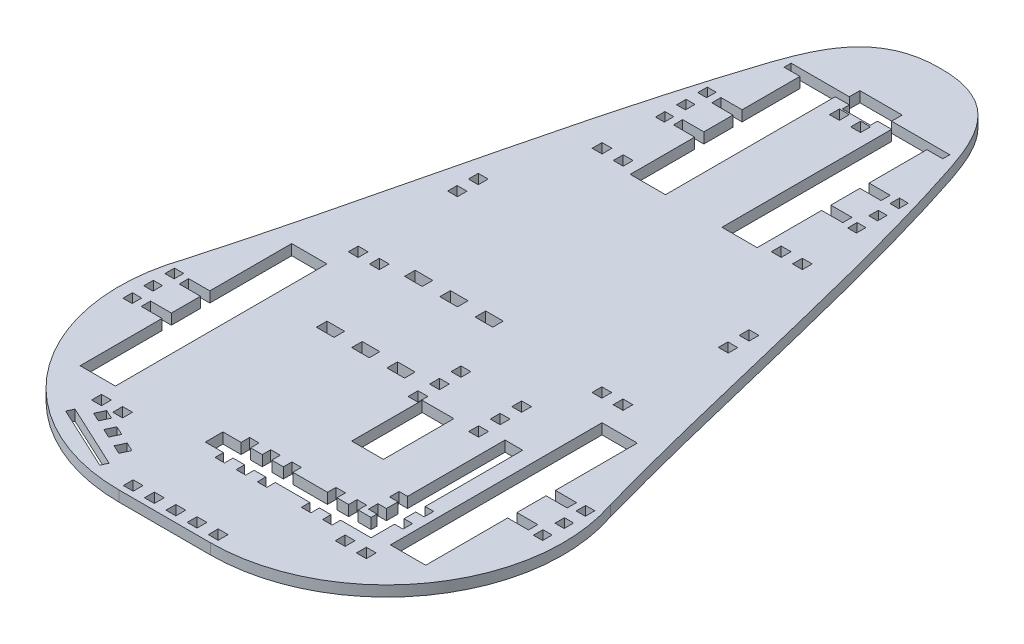
SolidWorks part; units mm, degrees
ref_plane "Front Plane" through (0, 0, 0) normal (0, 0, 1) x (1, 0, 0)
ref_plane "Top Plane" through (0, 0, 0) normal (0, 1, 0) x (1, 0, 0)
ref_plane "Right Plane" through (0, 0, 0) normal (1, 0, 0) x (0, 0, -1)
sketch "Sketch1" plane through (0, 0, 0) normal (0, 1, 0) x (1, 0, 0)
  line L0 (54.872, 210.7624) -> (54.872, -9.2376) construction
  line L1 (41.9035, -9.2376) -> (67.8405, -9.2376)
  line L6 (5.872, 75.7624) -> (15.872, 75.7624)
  line L7 (54.872, -9.2376) -> (64.872, -9.2376)
  line L8 (54.872, -9.2376) -> (44.872, -9.2376)
  line L9 (5.872, 75.7624) -> (5.872, 15.7624)
  line L10 (5.872, 15.7624) -> (15.872, 15.7624)
  line L11 (15.872, 75.7624) -> (15.872, 15.7624)
  line L12 (5.872, 75.7624) -> (15.872, 15.7624) construction
  line L13 (5.872, 15.7624) -> (15.872, 75.7624) construction
  line L18 (-0.128, 52.5374) -> (5.872, 52.5374)
  line L19 (-0.128, 52.5374) -> (-0.128, 49.8874)
  line L35 (103.872, 15.7624) -> (93.872, 15.7624)
  line L36 (93.872, 75.7624) -> (93.872, 15.7624)
  line L37 (103.872, 75.7624) -> (93.872, 75.7624)
  line L38 (103.872, 75.7624) -> (103.872, 15.7624)
  line L40 (36.872, 190.7624) -> (46.872, 190.7624)
  line L41 (36.872, 190.7624) -> (36.872, 140.7624)
  line L42 (36.872, 140.7624) -> (46.872, 140.7624)
  line L43 (46.872, 190.7624) -> (46.872, 140.7624)
  line L44 (36.872, 190.7624) -> (46.872, 140.7624) construction
  line L45 (36.872, 140.7624) -> (46.872, 190.7624) construction
  line L46 (10.872, 45.7624) -> (-10.2667, 45.7624) construction
  line L63 (72.872, 140.7624) -> (62.872, 140.7624)
  line L64 (62.872, 190.7624) -> (62.872, 140.7624)
  line L65 (72.872, 190.7624) -> (62.872, 190.7624)
  line L66 (72.872, 190.7624) -> (72.872, 140.7624)
  line L78 (114.472, 47.1124) -> (111.872, 44.4124) construction
  line L79 (114.472, 44.4124) -> (111.872, 47.1124) construction
  line L80 (114.472, 50.4124) -> (111.872, 53.1124) construction
  line L81 (114.472, 53.1124) -> (111.872, 50.4124) construction
  line L82 (109.7728, 38.9874) -> (103.7728, 41.6374) construction
  line L83 (109.7728, 41.6374) -> (103.7728, 38.9874) construction
  line L84 (109.872, 49.8874) -> (103.872, 52.5374) construction
  line L85 (109.872, 52.5374) -> (103.872, 49.8874) construction
  line L86 (111.7728, 41.1124) -> (111.7728, 38.4124)
  line L87 (114.3728, 38.4124) -> (111.7728, 38.4124)
  line L88 (114.3728, 41.1124) -> (114.3728, 38.4124)
  line L89 (111.872, 44.4124) -> (111.872, 47.1124)
  line L90 (114.472, 47.1124) -> (111.872, 47.1124)
  line L91 (114.472, 44.4124) -> (114.472, 47.1124)
  line L92 (41.872, 165.7624) -> (24.9145, 165.7624) construction
  line L93 (30.872, 172.4874) -> (36.872, 172.4874)
  line L94 (30.872, 172.4874) -> (30.872, 169.8874)
  line L95 (30.872, 169.8874) -> (36.872, 169.8874)
  line L96 (36.872, 172.4874) -> (36.872, 169.8874)
  line L97 (30.872, 172.4874) -> (36.872, 169.8874) construction
  line L98 (30.872, 169.8874) -> (36.872, 172.4874) construction
  line L103 (26.372, 161.1124) -> (28.872, 161.1124)
  line L104 (26.372, 173.1124) -> (28.872, 173.1124)
  line L105 (30.872, 161.6374) -> (36.872, 161.6374)
  line L106 (30.872, 161.6374) -> (30.872, 159.0374)
  line L107 (30.872, 159.0374) -> (36.872, 159.0374)
  line L108 (36.872, 161.6374) -> (36.872, 159.0374)
  line L109 (30.872, 161.6374) -> (36.872, 159.0374) construction
  line L110 (30.872, 159.0374) -> (36.872, 161.6374) construction
  line L111 (26.372, 173.1124) -> (26.372, 170.4124)
  line L112 (26.372, 170.4124) -> (28.872, 170.4124)
  line L113 (28.872, 173.1124) -> (28.872, 170.4124)
  line L114 (26.372, 173.1124) -> (28.872, 170.4124) construction
  line L115 (26.372, 170.4124) -> (28.872, 173.1124) construction
  line L116 (26.372, 164.4124) -> (28.872, 164.4124)
  line L117 (26.372, 164.4124) -> (26.372, 167.1124)
  line L118 (26.372, 167.1124) -> (28.872, 167.1124)
  line L119 (28.872, 164.4124) -> (28.872, 167.1124)
  line L120 (26.372, 164.4124) -> (28.872, 167.1124) construction
  line L121 (26.372, 167.1124) -> (28.872, 164.4124) construction
  line L122 (26.372, 161.1124) -> (26.372, 158.4124)
  line L123 (26.372, 158.4124) -> (28.872, 158.4124)
  line L124 (28.872, 161.1124) -> (28.872, 158.4124)
  line L125 (83.372, 167.1124) -> (80.872, 164.4124) construction
  line L126 (83.372, 164.4124) -> (80.872, 167.1124) construction
  line L127 (83.372, 170.4124) -> (80.872, 173.1124) construction
  line L128 (83.372, 173.1124) -> (80.872, 170.4124) construction
  line L129 (78.872, 159.0374) -> (72.872, 161.6374) construction
  line L130 (78.872, 161.6374) -> (72.872, 159.0374) construction
  line L131 (78.872, 169.8874) -> (72.872, 172.4874) construction
  line L132 (78.872, 172.4874) -> (72.872, 169.8874) construction
  line L133 (80.872, 161.1124) -> (80.872, 158.4124)
  line L134 (83.372, 158.4124) -> (80.872, 158.4124)
  line L135 (83.372, 161.1124) -> (83.372, 158.4124)
  line L136 (80.872, 164.4124) -> (80.872, 167.1124)
  line L137 (83.372, 167.1124) -> (80.872, 167.1124)
  line L138 (83.372, 164.4124) -> (83.372, 167.1124)
  line L139 (83.372, 164.4124) -> (80.872, 164.4124)
  line L140 (80.872, 173.1124) -> (80.872, 170.4124)
  line L141 (83.372, 170.4124) -> (80.872, 170.4124)
  line L142 (83.372, 173.1124) -> (83.372, 170.4124)
  line L143 (72.872, 161.6374) -> (72.872, 159.0374)
  line L144 (78.872, 159.0374) -> (72.872, 159.0374)
  line L145 (78.872, 161.6374) -> (78.872, 159.0374)
  line L146 (78.872, 161.6374) -> (72.872, 161.6374)
  line L147 (83.372, 173.1124) -> (80.872, 173.1124)
  line L148 (83.372, 161.1124) -> (80.872, 161.1124)
  line L149 (72.872, 172.4874) -> (72.872, 169.8874)
  line L150 (78.872, 169.8874) -> (72.872, 169.8874)
  line L151 (78.872, 172.4874) -> (78.872, 169.8874)
  line L152 (78.872, 172.4874) -> (72.872, 172.4874)
  line L153 (-0.128, 49.8874) -> (5.872, 49.8874)
  line L154 (5.872, 52.5374) -> (5.872, 49.8874)
  line L155 (-0.128, 52.5374) -> (5.872, 49.8874) construction
  line L156 (-0.128, 49.8874) -> (5.872, 52.5374) construction
  line L157 (-4.6289, 41.1124) -> (-2.0289, 41.1124)
  line L158 (-4.728, 53.1124) -> (-2.128, 53.1124)
  line L159 (-0.0289, 41.6374) -> (5.9711, 41.6374)
  line L160 (-0.0289, 41.6374) -> (-0.0289, 38.9874)
  line L161 (-0.0289, 38.9874) -> (5.9711, 38.9874)
  line L162 (5.9711, 41.6374) -> (5.9711, 38.9874)
  line L163 (-0.0289, 41.6374) -> (5.9711, 38.9874) construction
  line L164 (-0.0289, 38.9874) -> (5.9711, 41.6374) construction
  line L165 (-4.728, 53.1124) -> (-4.728, 50.4124)
  line L166 (-4.728, 50.4124) -> (-2.128, 50.4124)
  line L167 (-2.128, 53.1124) -> (-2.128, 50.4124)
  line L168 (-4.728, 53.1124) -> (-2.128, 50.4124) construction
  line L169 (-4.728, 50.4124) -> (-2.128, 53.1124) construction
  line L170 (-4.728, 44.4124) -> (-2.128, 44.4124)
  line L171 (-4.728, 44.4124) -> (-4.728, 47.1124)
  line L172 (-4.728, 47.1124) -> (-2.128, 47.1124)
  line L173 (-2.128, 44.4124) -> (-2.128, 47.1124)
  line L174 (-4.728, 44.4124) -> (-2.128, 47.1124) construction
  line L175 (-4.728, 47.1124) -> (-2.128, 44.4124) construction
  line L176 (-4.6289, 41.1124) -> (-4.6289, 38.4124)
  line L177 (-4.6289, 38.4124) -> (-2.0289, 38.4124)
  line L178 (-2.0289, 41.1124) -> (-2.0289, 38.4124)
  line L179 (114.472, 44.4124) -> (111.872, 44.4124)
  line L180 (111.872, 53.1124) -> (111.872, 50.4124)
  line L181 (114.472, 50.4124) -> (111.872, 50.4124)
  line L182 (114.472, 53.1124) -> (114.472, 50.4124)
  line L183 (103.7728, 41.6374) -> (103.7728, 38.9874)
  line L184 (109.7728, 38.9874) -> (103.7728, 38.9874)
  line L185 (109.7728, 41.6374) -> (109.7728, 38.9874)
  line L186 (109.7728, 41.6374) -> (103.7728, 41.6374)
  line L187 (114.472, 53.1124) -> (111.872, 53.1124)
  line L188 (114.3728, 41.1124) -> (111.7728, 41.1124)
  line L189 (103.872, 52.5374) -> (103.872, 49.8874)
  line L190 (109.872, 49.8874) -> (103.872, 49.8874)
  line L191 (109.872, 52.5374) -> (109.872, 49.8874)
  line L192 (109.872, 52.5374) -> (103.872, 52.5374)
  line L193 (103.872, 45.7624) -> (5.872, 45.7624) construction
  line L200 (62.872, 55.7624) -> (71.872, 55.7624)
  line L201 (62.872, 55.7624) -> (62.872, 35.7624)
  line L202 (62.872, 35.7624) -> (71.872, 35.7624)
  line L203 (71.872, 55.7624) -> (71.872, 35.7624)
  line L204 (62.872, 55.7624) -> (71.872, 35.7624) construction
  line L205 (62.872, 35.7624) -> (71.872, 55.7624) construction
  line L211 (39.9211, 61.7172) -> (44.9211, 61.7172)
  line L213 (59.9211, 69.7172) -> (62.7211, 69.7172)
  line L214 (59.9211, 57.5172) -> (62.7211, 57.5172)
  line L215 (59.9211, 57.5172) -> (59.9211, 54.7172)
  line L216 (59.9211, 54.7172) -> (62.7211, 54.7172)
  line L217 (62.7211, 57.5172) -> (62.7211, 54.7172)
  line L218 (59.9211, 57.5172) -> (62.7211, 54.7172) construction
  line L219 (59.9211, 54.7172) -> (62.7211, 57.5172) construction
  line L220 (59.9211, 69.7172) -> (59.9211, 66.9172)
  line L221 (59.9211, 66.9172) -> (62.7211, 66.9172)
  line L222 (62.7211, 69.7172) -> (62.7211, 66.9172)
  line L223 (59.9211, 63.6172) -> (62.7211, 63.6172)
  line L224 (59.9211, 63.6172) -> (59.9211, 60.8172)
  line L225 (59.9211, 60.8172) -> (62.7211, 60.8172)
  line L226 (62.7211, 63.6172) -> (62.7211, 60.8172)
  line L227 (77.1211, 69.7172) -> (79.9211, 69.7172)
  line L228 (77.1211, 57.5172) -> (79.9211, 57.5172)
  line L229 (77.1211, 57.5172) -> (77.1211, 54.7172)
  line L230 (77.1211, 54.7172) -> (79.9211, 54.7172)
  line L231 (79.9211, 57.5172) -> (79.9211, 54.7172)
  line L232 (77.1211, 69.7172) -> (77.1211, 66.9172)
  line L233 (77.1211, 66.9172) -> (79.9211, 66.9172)
  line L234 (79.9211, 69.7172) -> (79.9211, 66.9172)
  line L235 (77.1211, 63.6172) -> (79.9211, 63.6172)
  line L236 (77.1211, 63.6172) -> (77.1211, 60.8172)
  line L237 (77.1211, 60.8172) -> (79.9211, 60.8172)
  line L238 (79.9211, 63.6172) -> (79.9211, 60.8172)
  line L244 (49.9211, 61.7172) -> (54.9211, 61.7172)
  line L245 (49.9211, 61.7172) -> (49.9211, 58.7172)
  line L246 (49.9211, 58.7172) -> (54.9211, 58.7172)
  line L247 (54.9211, 61.7172) -> (54.9211, 58.7172)
  line L248 (49.9211, 61.7172) -> (54.9211, 58.7172) construction
  line L249 (49.9211, 58.7172) -> (54.9211, 61.7172) construction
  line L250 (39.9211, 61.7172) -> (39.9211, 58.7172)
  line L251 (39.9211, 58.7172) -> (44.9211, 58.7172)
  line L252 (44.9211, 61.7172) -> (44.9211, 58.7172)
  line L253 (29.9211, 61.7172) -> (34.9211, 61.7172)
  line L254 (29.9211, 61.7172) -> (29.9211, 58.7172)
  line L255 (29.9211, 58.7172) -> (34.9211, 58.7172)
  line L256 (34.9211, 61.7172) -> (34.9211, 58.7172)
  line L257 (49.9211, 86.7172) -> (54.9211, 86.7172)
  line L258 (49.9211, 86.7172) -> (49.9211, 83.7172)
  line L259 (49.9211, 83.7172) -> (54.9211, 83.7172)
  line L260 (54.9211, 86.7172) -> (54.9211, 83.7172)
  line L261 (39.9211, 86.7172) -> (44.9211, 86.7172)
  line L262 (39.9211, 86.7172) -> (39.9211, 83.7172)
  line L263 (39.9211, 83.7172) -> (44.9211, 83.7172)
  line L264 (44.9211, 86.7172) -> (44.9211, 83.7172)
  line L265 (29.9211, 86.7172) -> (34.9211, 86.7172)
  line L266 (29.9211, 86.7172) -> (29.9211, 83.7172)
  line L267 (29.9211, 83.7172) -> (34.9211, 83.7172)
  line L268 (34.9211, 86.7172) -> (34.9211, 83.7172)
  line L279 (15.072, 113.4624) -> (17.872, 113.4624)
  line L284 (15.0729, 119.4624) -> (17.8729, 119.4624)
  line L285 (15.0729, 119.4624) -> (15.0729, 116.6624)
  line L286 (15.0729, 116.6624) -> (17.8729, 116.6624)
  line L287 (17.8729, 119.4624) -> (17.8729, 116.6624)
  line L288 (15.072, 113.4624) -> (15.072, 110.7624)
  line L289 (15.072, 110.7624) -> (17.872, 110.7624)
  line L290 (17.872, 113.4624) -> (17.872, 110.7624)
  line L291 (318.4893, 36.945) -> (321.2893, 36.945)
  line L292 (243.2893, 39.945) -> (321.2893, 39.945)
  line L293 (243.2893, 39.945) -> (243.2893, -41.655)
  line L294 (243.2893, -41.655) -> (321.2893, -41.655)
  line L295 (321.2893, 39.945) -> (321.2893, -41.655)
  line L296 (243.2893, 36.945) -> (246.0893, 36.945)
  line L297 (243.2893, 36.945) -> (243.2893, 34.145)
  line L298 (243.2893, 34.145) -> (246.0893, 34.145)
  line L299 (246.0893, 36.945) -> (246.0893, 34.145)
  line L300 (318.4893, 36.945) -> (318.4893, 34.145)
  line L301 (318.4893, 34.145) -> (321.2893, 34.145)
  line L302 (321.2893, 36.945) -> (321.2893, 34.145)
  line L303 (249.2893, 36.945) -> (252.0893, 36.945)
  line L304 (249.2893, 36.945) -> (249.2893, 34.145)
  line L305 (249.2893, 34.145) -> (252.0893, 34.145)
  line L306 (252.0893, 36.945) -> (252.0893, 34.145)
  line L307 (312.4893, 36.945) -> (315.2893, 36.945)
  line L308 (312.4893, 36.945) -> (312.4893, 34.145)
  line L309 (312.4893, 34.145) -> (315.2893, 34.145)
  line L310 (315.2893, 36.945) -> (315.2893, 34.145)
  line L311 (318.4893, -35.855) -> (321.2893, -35.855)
  line L312 (243.2893, -35.855) -> (246.0893, -35.855)
  line L313 (243.2893, -35.855) -> (243.2893, -38.655)
  line L314 (243.2893, -38.655) -> (246.0893, -38.655)
  line L315 (246.0893, -35.855) -> (246.0893, -38.655)
  line L316 (318.4893, -35.855) -> (318.4893, -38.655)
  line L317 (318.4893, -38.655) -> (321.2893, -38.655)
  line L318 (321.2893, -35.855) -> (321.2893, -38.655)
  line L319 (249.2893, -35.855) -> (252.0893, -35.855)
  line L320 (249.2893, -35.855) -> (249.2893, -38.655)
  line L321 (249.2893, -38.655) -> (252.0893, -38.655)
  line L322 (252.0893, -35.855) -> (252.0893, -38.655)
  line L323 (312.4893, -35.855) -> (315.2893, -35.855)
  line L324 (312.4893, -35.855) -> (312.4893, -38.655)
  line L325 (312.4893, -38.655) -> (315.2893, -38.655)
  line L326 (315.2893, -35.855) -> (315.2893, -38.655)
  line L332 (15.9201, 84.5624) -> (18.7201, 84.5624)
  line L333 (15.9201, 84.5624) -> (15.9201, 81.7624)
  line L334 (15.9201, 81.7624) -> (18.7201, 81.7624)
  line L335 (18.7201, 84.5624) -> (18.7201, 81.7624)
  line L339 (21.9201, 84.5624) -> (24.7201, 84.5624)
  line L340 (21.9201, 84.5624) -> (21.9201, 81.7624)
  line L341 (21.9201, 81.7624) -> (24.7201, 81.7624)
  line L342 (24.7201, 84.5624) -> (24.7201, 81.7624)
  line L348 (15.9201, 11.7624) -> (18.7201, 11.7624)
  line L349 (15.9201, 11.7624) -> (15.9201, 8.9624)
  line L350 (15.9201, 8.9624) -> (18.7201, 8.9624)
  line L351 (18.7201, 11.7624) -> (18.7201, 8.9624)
  line L355 (21.9201, 11.7624) -> (24.7201, 11.7624)
  line L356 (21.9201, 11.7624) -> (21.9201, 8.9624)
  line L357 (21.9201, 8.9624) -> (24.7201, 8.9624)
  line L358 (24.7201, 11.7624) -> (24.7201, 8.9624)
  line L363 (25.072, 144.5629) -> (27.872, 144.5629)
  line L368 (25.072, 144.5629) -> (25.072, 141.7629)
  line L369 (25.072, 141.7629) -> (27.872, 141.7629)
  line L370 (27.872, 144.5629) -> (27.872, 141.7629)
  line L371 (31.072, 144.5624) -> (33.872, 144.5624)
  line L372 (31.072, 144.5624) -> (31.072, 141.7624)
  line L373 (31.072, 141.7624) -> (33.872, 141.7624)
  line L374 (33.872, 144.5624) -> (33.872, 141.7624)
  line L375 (75.872, 144.5624) -> (75.872, 141.7624)
  line L376 (78.672, 141.7624) -> (75.872, 141.7624)
  line L377 (78.672, 144.5624) -> (78.672, 141.7624)
  line L378 (78.672, 144.5624) -> (75.872, 144.5624)
  line L379 (81.872, 144.5629) -> (81.872, 141.7629)
  line L380 (84.672, 141.7629) -> (81.872, 141.7629)
  line L381 (84.672, 144.5629) -> (84.672, 141.7629)
  line L382 (84.672, 144.5629) -> (81.872, 144.5629)
  line L383 (50.4739, 186.4794) -> (50.472, 183.6794)
  line L384 (32.372, 190.884) -> (77.372, 190.884)
  line L385 (32.372, 190.884) -> (32.372, 188.884)
  line L386 (32.372, 188.884) -> (77.372, 188.884)
  line L387 (77.372, 190.884) -> (77.372, 188.884)
  line L388 (48.872, 193.884) -> (60.872, 193.884)
  line L389 (48.872, 193.884) -> (48.872, 190.884)
  line L390 (48.872, 190.884) -> (60.872, 190.884)
  line L391 (60.872, 193.884) -> (60.872, 190.884)
  line L392 (53.272, 183.6794) -> (50.472, 183.6794)
  line L393 (53.272, 186.4794) -> (53.272, 183.6794)
  line L394 (53.272, 186.4794) -> (50.4739, 186.4794)
  line L404 (85.372, 55.7624) -> (88.372, 55.7624)
  line L405 (85.372, 55.7624) -> (85.372, 15.7624)
  line L406 (85.372, 15.7624) -> (88.372, 15.7624)
  line L407 (88.372, 55.7624) -> (88.372, 15.7624)
  line L408 (44.372, 18.7624) -> (88.372, 18.7624)
  line L409 (44.372, 18.7624) -> (44.372, 15.7624)
  line L410 (44.372, 15.7624) -> (88.372, 15.7624)
  line L411 (88.372, 18.7624) -> (88.372, 15.7624)
  line L471 (41.9035, -9.2376) -> (64.872, -9.2376)
  line L480 (47.522, 22.1624) -> (47.522, 19.7624)
  line L481 (50.222, 19.7624) -> (47.522, 19.7624)
  line L482 (50.222, 22.1624) -> (50.222, 19.7624)
  line L483 (50.222, 22.1624) -> (47.522, 22.1624)
  line L484 (53.522, 22.1624) -> (53.522, 19.7624)
  line L485 (56.222, 19.7624) -> (53.522, 19.7624)
  line L486 (56.222, 22.1624) -> (56.222, 19.7624)
  line L487 (56.222, 22.1624) -> (53.522, 22.1624)
  line L488 (59.522, 22.1624) -> (59.522, 19.7624)
  line L489 (62.222, 19.7624) -> (59.522, 19.7624)
  line L490 (62.222, 22.1624) -> (62.222, 19.7624)
  line L491 (62.222, 22.1624) -> (59.522, 22.1624)
  line L492 (56.472, 186.4794) -> (59.2701, 186.4794)
  line L493 (56.472, 186.4794) -> (56.472, 183.6794)
  line L494 (56.472, 183.6794) -> (59.272, 183.6794)
  line L495 (59.2701, 186.4794) -> (59.272, 183.6794)
  line L496 (94.672, 113.4624) -> (94.672, 110.7624)
  line L497 (94.672, 110.7624) -> (91.872, 110.7624)
  line L498 (91.872, 113.4624) -> (91.872, 110.7624)
  line L499 (94.672, 113.4624) -> (91.872, 113.4624)
  line L500 (94.671, 119.4624) -> (94.671, 116.6624)
  line L501 (94.671, 116.6624) -> (91.871, 116.6624)
  line L502 (91.871, 119.4624) -> (91.871, 116.6624)
  line L503 (94.671, 119.4624) -> (91.871, 119.4624)
  line L504 (87.8238, 11.7624) -> (87.8238, 8.9624)
  line L505 (87.8238, 8.9624) -> (85.0238, 8.9624)
  line L506 (85.0238, 11.7624) -> (85.0238, 8.9624)
  line L507 (87.8238, 11.7624) -> (85.0238, 11.7624)
  line L508 (93.8238, 11.7624) -> (93.8238, 8.9624)
  line L509 (93.8238, 8.9624) -> (91.0238, 8.9624)
  line L510 (91.0238, 11.7624) -> (91.0238, 8.9624)
  line L511 (93.8238, 11.7624) -> (91.0238, 11.7624)
  line L512 (87.8238, 84.5624) -> (87.8238, 81.7624)
  line L513 (87.8238, 81.7624) -> (85.0238, 81.7624)
  line L514 (85.0238, 84.5624) -> (85.0238, 81.7624)
  line L515 (87.8238, 84.5624) -> (85.0238, 84.5624)
  line L516 (93.8238, 84.5624) -> (93.8238, 81.7624)
  line L517 (93.8238, 81.7624) -> (91.0238, 81.7624)
  line L518 (91.0238, 84.5624) -> (91.0238, 81.7624)
  line L519 (93.8238, 84.5624) -> (91.0238, 84.5624)
  line L520 (76.372, 18.7624) -> (76.372, 15.7624) construction
  line L521 (64.372, 18.7624) -> (88.372, 18.7624)
  line L522 (64.372, 18.7624) -> (64.372, 15.7624)
  line L523 (64.372, 15.7624) -> (88.372, 15.7624)
  line L524 (88.372, 18.7624) -> (88.372, 15.7624)
  line L525 (76.372, 27.5136) -> (76.372, 8.1564) construction
  line L526 (85.372, 25.7624) -> (88.372, 25.7624) construction
  line L527 (85.372, 35.7624) -> (88.372, 35.7624)
  line L528 (85.372, 35.7624) -> (85.372, 15.7624)
  line L529 (85.372, 15.7624) -> (88.372, 15.7624)
  line L530 (88.372, 35.7624) -> (88.372, 15.7624)
  line L531 (91.4767, 25.7624) -> (69.6189, 25.7624) construction
  line L532 (44.372, 17.2624) -> (64.372, 17.2624) construction
  line L537 (84.372, 57.7624) -> (89.372, 57.7624)
  line L538 (84.372, 57.7624) -> (84.372, 14.7624)
  line L539 (84.372, 14.7624) -> (89.372, 14.7624)
  line L540 (89.372, 57.7624) -> (89.372, 14.7624)
  line L541 (42.372, 19.7624) -> (89.372, 19.7624)
  line L542 (42.372, 19.7624) -> (42.372, 14.7624)
  line L543 (42.372, 14.7624) -> (89.372, 14.7624)
  line L544 (89.372, 19.7624) -> (89.372, 14.7624)
  line L545 (74.722, 14.7624) -> (74.722, 12.3624)
  line L546 (74.722, 12.3624) -> (72.022, 12.3624)
  line L547 (72.022, 14.7624) -> (72.022, 12.3624)
  line L548 (74.722, 14.7624) -> (72.022, 14.7624)
  line L553 (80.722, 14.7624) -> (80.722, 12.3624)
  line L554 (78.022, 14.7624) -> (80.722, 14.7624)
  line L555 (78.022, 14.7624) -> (78.022, 12.3624)
  line L556 (78.022, 12.3624) -> (80.722, 12.3624)
  line L557 (64.372, 17.2624) -> (88.372, 17.2624) construction
  line L558 (78.022, 19.7624) -> (80.722, 19.7624)
  line L559 (78.022, 19.7624) -> (78.022, 22.1624)
  line L560 (78.022, 22.1624) -> (80.722, 22.1624)
  line L561 (80.722, 19.7624) -> (80.722, 22.1624)
  line L562 (72.022, 19.7624) -> (72.022, 22.1624)
  line L563 (74.722, 19.7624) -> (72.022, 19.7624)
  line L564 (74.722, 19.7624) -> (74.722, 22.1624)
  line L565 (74.722, 22.1624) -> (72.022, 22.1624)
  line L566 (81.972, 27.4124) -> (84.372, 27.4124)
  line L567 (81.972, 27.4124) -> (81.972, 30.1124)
  line L568 (81.972, 30.1124) -> (84.372, 30.1124)
  line L569 (84.372, 27.4124) -> (84.372, 30.1124)
  line L574 (86.872, 35.7624) -> (86.872, 15.7624) construction
  line L575 (81.972, 24.1124) -> (81.972, 21.4124)
  line L576 (81.972, 21.4124) -> (84.372, 21.4124)
  line L577 (84.372, 24.1124) -> (84.372, 21.4124)
  line L578 (81.972, 24.1124) -> (84.372, 24.1124)
  line L579 (91.772, 24.1124) -> (89.372, 24.1124)
  line L580 (89.372, 24.1124) -> (89.372, 21.4124)
  line L581 (91.772, 21.4124) -> (89.372, 21.4124)
  line L582 (91.772, 24.1124) -> (91.772, 21.4124)
  line L583 (91.772, 27.4124) -> (91.772, 30.1124)
  line L584 (91.772, 30.1124) -> (89.372, 30.1124)
  line L585 (89.372, 27.4124) -> (89.372, 30.1124)
  line L586 (91.772, 27.4124) -> (89.372, 27.4124)
  line L588 (50.872, 188.884) -> (58.872, 188.884)
  line L589 (50.872, 188.884) -> (50.872, 186.884)
  line L590 (50.872, 186.884) -> (58.872, 186.884)
  line L591 (58.872, 188.884) -> (58.872, 186.884)
  line L659 (24.863, 0.1599) -> (24.0178, -1.6527) construction
  line L660 (59.522, -4.7376) -> (62.322, -4.7376)
  line L661 (53.522, -4.7376) -> (56.322, -4.7376)
  line L662 (53.522, -4.7376) -> (53.522, -7.5376)
  line L663 (53.522, -7.5376) -> (56.322, -7.5376)
  line L664 (56.322, -4.7376) -> (56.322, -7.5376)
  line L665 (59.522, -4.7376) -> (59.522, -7.5376)
  line L666 (59.522, -7.5376) -> (62.322, -7.5376)
  line L667 (62.322, -4.7376) -> (62.322, -7.5376)
  line L668 (65.522, -4.7376) -> (68.322, -4.7376)
  line L669 (65.522, -4.7376) -> (65.522, -7.5376)
  line L670 (65.522, -7.5376) -> (68.322, -7.5376)
  line L671 (68.322, -4.7376) -> (68.322, -7.5376)
  line L672 (44.222, -4.7376) -> (44.222, -7.5376)
  line L673 (44.222, -7.5376) -> (41.422, -7.5376)
  line L674 (41.422, -4.7376) -> (41.422, -7.5376)
  line L675 (44.222, -4.7376) -> (41.422, -4.7376)
  line L676 (50.222, -4.7376) -> (50.222, -7.5376)
  line L677 (50.222, -7.5376) -> (47.422, -7.5376)
  line L678 (47.422, -4.7376) -> (47.422, -7.5376)
  line L679 (50.222, -4.7376) -> (47.422, -4.7376)
  line L689 (20.6529, 8.5227) -> (19.4695, 5.9851)
  line L690 (22.0072, 4.8017) -> (19.4695, 5.9851)
  line L691 (14.9547, 2.5735) -> (33.0809, -5.8789)
  line L692 (14.9547, 2.5735) -> (15.8, 4.3861)
  line L693 (15.8, 4.3861) -> (33.9261, -4.0663)
  line L694 (33.0809, -5.8789) -> (33.9261, -4.0663)
  line L698 (23.1905, 7.3394) -> (22.0072, 4.8017)
  line L699 (23.1905, 7.3394) -> (20.6529, 8.5227)
  line L700 (26.0907, 5.987) -> (24.9074, 3.4493)
  line L701 (27.445, 2.266) -> (24.9074, 3.4493)
  line L702 (28.6284, 4.8037) -> (27.445, 2.266)
  line L703 (28.6284, 4.8037) -> (26.0907, 5.987)
  line L704 (31.5286, 3.4513) -> (30.3452, 0.9136)
  line L705 (32.8829, -0.2697) -> (30.3452, 0.9136)
  line L706 (34.0662, 2.268) -> (32.8829, -0.2697)
  line L707 (34.0662, 2.268) -> (31.5286, 3.4513)
  line L708 (62.222, 12.3624) -> (59.522, 12.3624)
  line L709 (62.222, 12.3624) -> (62.222, 14.7624)
  line L710 (62.222, 14.7624) -> (59.522, 14.7624)
  line L711 (59.522, 12.3624) -> (59.522, 14.7624)
  line L712 (56.222, 12.3624) -> (53.522, 12.3624)
  line L713 (56.222, 12.3624) -> (56.222, 14.7624)
  line L714 (56.222, 14.7624) -> (53.522, 14.7624)
  line L715 (53.522, 12.3624) -> (53.522, 14.7624)
  line L716 (50.222, 12.3624) -> (47.522, 12.3624)
  line L717 (50.222, 12.3624) -> (50.222, 14.7624)
  line L718 (50.222, 14.7624) -> (47.522, 14.7624)
  line L719 (47.522, 12.3624) -> (47.522, 14.7624)
  arc A0 (41.9035, -9.2376) -> (-5.452, 56.8081) centre (41.9035, 40.7624) cw
  arc A1 (67.8405, -9.2376) -> (115.1959, 56.8081) centre (67.8405, 40.7624) ccw
  spline S0 degree 3 poles (54.872, 210.7624) (53.982, 210.7624) (36.6831, 210.353) (26.6517, 181.7608) (12.4717, 130.3178) (2.6705, 85.557) (-5.452, 56.8081) knots 0 0 0 0 0.011072 0.22144 0.460221 1 1 1 1
  spline S1 degree 3 poles (54.872, 210.7624) (55.7619, 210.7624) (73.0609, 210.353) (83.0922, 181.7608) (97.2722, 130.3178) (107.0734, 85.557) (115.1959, 56.8081) knots 0 0 0 0 0.011072 0.22144 0.460221 1 1 1 1
  point P4 (2.872, 51.2124)
  point P24 (10.872, 45.7624)
  point P30 (-3.428, 51.7624)
  point P33 (2.9711, 40.3124)
  point P40 (-3.428, 45.7624)
  point P50 (41.872, 165.7624)
  point P67 (33.872, 171.1874)
  point P82 (27.622, 171.7624)
  point P85 (33.872, 160.3374)
  point P92 (27.622, 165.7624)
  point P121 (82.122, 165.7624)
  point P122 (75.872, 160.3374)
  point P123 (82.122, 171.7624)
  point P124 (75.872, 171.1874)
  point P131 (113.172, 45.7624)
  point P132 (106.7728, 40.3124)
  point P133 (113.172, 51.7624)
  point P134 (106.872, 51.2124)
  point P141 (67.372, 45.7624)
  point P151 (61.3211, 56.1172)
  point P177 (52.4211, 60.2172)
  point P370 (24.4404, -0.7464)
  dimension "D6" = 10
  dimension "D7" = 50
  dimension "D10" = 6
  dimension "D2" = 173.1277
  dimension "D1" = 220
  dimension "D3" = 60.3239
  dimension "D4" = 10
  dimension "D5" = 10
  dimension "D8" = 60
  dimension "D9" = 6
  dimension "D11" = 25
  dimension "D12" = 2.6
  dimension "D13" = 2.7
  dimension "D14" = 2.6
  dimension "D15" = 2.7
  dimension "D16" = 2
  dimension "D17" = 2
  dimension "D18" = 39
  dimension "D19" = 2.6
  dimension "D20" = 10
  dimension "D21" = 50
  dimension "D22" = 20
  dimension "D23" = 8
  dimension "D24" = 8.25
  dimension "D25" = 0
  dimension "D26" = 0
  dimension "D27" = 3.3
  dimension "D28" = 3.3
  dimension "D29" = 8.25
  dimension "D30" = 4.125
  dimension "D31" = 2.5
  dimension "D32" = 2.7
  dimension "D33" = 2.7
  dimension "D34" = 6
  dimension "D35" = 2.6
  dimension "D36" = 8.25
  dimension "D37" = 4.125
  dimension "D38" = 2.6
  dimension "D39" = 6
  dimension "D40" = 0
  dimension "D41" = 0
  dimension "D42" = 2.5
  dimension "D43" = 2.7
  dimension "D44" = 2.5
  dimension "D45" = 2.7
  dimension "D46" = 2
  dimension "D47" = 2
  dimension "D48" = 3.3
  dimension "D49" = 2.5
  dimension "D50" = 2.7
  dimension "D51" = 3
  dimension "0.33" = 3.3
  dimension "D52" = 2
  dimension "D53" = 52
  dimension "D54" = 2
  dimension "D55" = 2.65
  dimension "D56" = 2.8
  dimension "D57" = 9
  dimension "D58" = 20
  dimension "D59" = 10
  dimension "D60" = 47
  dimension "D61" = 24
  dimension "D62" = 0
  dimension "D63" = 2.8
  dimension "D64" = 2.8
  dimension "D65" = 0
  dimension "D66" = 5
  dimension "D67" = 3
  dimension "D68" = 3
  dimension "D69" = 20
  dimension "D70" = 3.3
  dimension "D71" = 2.8
  dimension "D72" = 2.8
  dimension "D73" = 3.3
  dimension "D74" = 2.8
  dimension "D75" = 2.8
  dimension "D76" = 2.8
  dimension "D77" = 2.8
  dimension "D78" = 2.8
  dimension "D79" = 2.8
  dimension "D80" = 3.3
  dimension "D81" = 3.3
  dimension "D82" = 0
  dimension "D83" = 5
  dimension "D84" = 3
  dimension "D85" = 5
  dimension "D86" = 0
  dimension "D87" = 5
  dimension "D88" = 5
  dimension "D89" = 3
  dimension "D90" = 5
  dimension "D91" = 3
  dimension "D92" = 2.8
  dimension "D93" = 2.8
  dimension "D94" = 5
  dimension "D95" = 3
  dimension "D96" = 2.7
  dimension "D97" = 5
  dimension "D98" = 5
  dimension "D99" = 3
  dimension "D100" = 2.8
  dimension "D101" = 5
  dimension "D102" = 3.2
  dimension "D103" = 0.001
  dimension "D104" = 37
  dimension "D105" = 30
  dimension "D106" = 78
  dimension "D107" = 81.6
  dimension "D108" = 2.8
  dimension "D109" = 2.8
  dimension "D110" = 3
  dimension "D111" = 0
  dimension "D112" = 2.8
  dimension "D113" = 2.8
  dimension "D114" = 3
  dimension "D115" = 3.2
  dimension "D116" = 2.8
  dimension "D117" = 2.8
  dimension "D118" = 2.8
  dimension "D119" = 0
  dimension "D120" = 2.8
  dimension "D121" = 2.8
  dimension "D122" = 2.8
  dimension "D123" = 3.2
  dimension "D124" = 3.2
  dimension "D125" = 2.8
  dimension "D126" = 2.8
  dimension "D127" = 2.8
  dimension "D128" = 2.8
  dimension "D129" = 3.2
  dimension "D130" = 2.8
  dimension "D131" = 2.8
  dimension "D132" = 0
  dimension "D133" = 0
  dimension "D134" = 3
  dimension "D135" = 3
  dimension "D136" = 70
  dimension "D137" = 2.8
  dimension "0.28" = 2.8
  dimension "D139" = 2.8
  dimension "D140" = 2.8
  dimension "D141" = 2.8
  dimension "D142" = 2.8
  dimension "D143" = 3.2
  dimension "D144" = 3.2
  dimension "D145" = 2
  dimension "D146" = 2.8
  dimension "D147" = 5
  dimension "D148" = 43
  dimension "D149" = 5
  dimension "D150" = 3.2
  dimension "D151" = 1
  dimension "D152" = 2.8
  dimension "D153" = 2.8
  dimension "D154" = 3.2
  dimension "D155" = 2.8
  dimension "D156" = 2.8
  dimension "D157" = 47
  dimension "D158" = 12.5
  dimension "D159" = 4.5
  dimension "D160" = 18
  dimension "D161" = 2.5
  dimension "D162" = 3
  dimension "D163" = 45
  dimension "D164" = 2
  dimension "D165" = 22.5
  dimension "D166" = 70
  dimension "D167" = 12
  dimension "D168" = 3
  dimension "D169" = 0
  dimension "D170" = 6
  dimension "D171" = 2.8
  dimension "D172" = 2.8
  dimension "D173" = 0
  dimension "D174" = 0
  dimension "D175" = 0
  dimension "D176" = 1.6
  dimension "D178" = 2.65
  dimension "D179" = 2.4
  dimension "D180" = 2.7
  dimension "D181" = 3
  dimension "D182" = 40
  dimension "D183" = 10
  dimension "D184" = 3
  dimension "D185" = 44
  dimension "D186" = 5.5
  dimension "D187" = 0
  dimension "D188" = 0
  dimension "D189" = 2.4
  dimension "D190" = 2.7
  dimension "D191" = 1.65
  dimension "D192" = 0
  dimension "D195" = 20
  dimension "D196" = 3.2
  dimension "D197" = 2.8
  dimension "D198" = 2.8
  dimension "D199" = 2.8
  dimension "D200" = 2.8
  dimension "D201" = 0
  dimension "D202" = 4
  dimension "D203" = 2.8
  dimension "D205" = 0
  dimension "D210" = 2.7
  dimension "D211" = 2.4
  dimension "D212" = 2.7
  dimension "D213" = 2.4
  dimension "D214" = 2.7
  dimension "D215" = 2.4
  dimension "D216" = 1.35
  dimension "D217" = 2.4
  dimension "D218" = 2.4
  dimension "D219" = 2.4
  dimension "D220" = 2.4
  dimension "D221" = 2.7
  dimension "D222" = 2.7
  dimension "D223" = 1.65
  dimension "D224" = 0
  dimension "D225" = 2.4
  dimension "D226" = 8
  dimension "D227" = 4
  dimension "D228" = 2
  dimension "D229" = 0
  dimension "D230" = 2.8
  dimension "D231" = 2.8
  dimension "D232" = 2.8
  dimension "D233" = 2.8
  dimension "D234" = 0
  dimension "D235" = 2.8
  dimension "D236" = 3.3
  dimension "D237" = 2.7
  dimension "D238" = 2.7
  dimension "D239" = 3.3
  dimension "D240" = 180
  dimension "D241" = 1.35
  dimension "D242" = 1.35
  dimension "D243" = 3.2
  dimension "D244" = 2.8
  dimension "D245" = 3.2
  dimension "D246" = 3
  dimension "D247" = 2.8
  dimension "D248" = 2
  dimension "D249" = 46
  dimension "D250" = 30.4315
  dimension "D138" = 2.8
extrude "Boss-Extrude1" add sketch "Sketch1" along normal blind 3 contours L0 S0 A0 L1 | S1 L0 L1 A1 region at (3.3293, 0, -13.1044)
